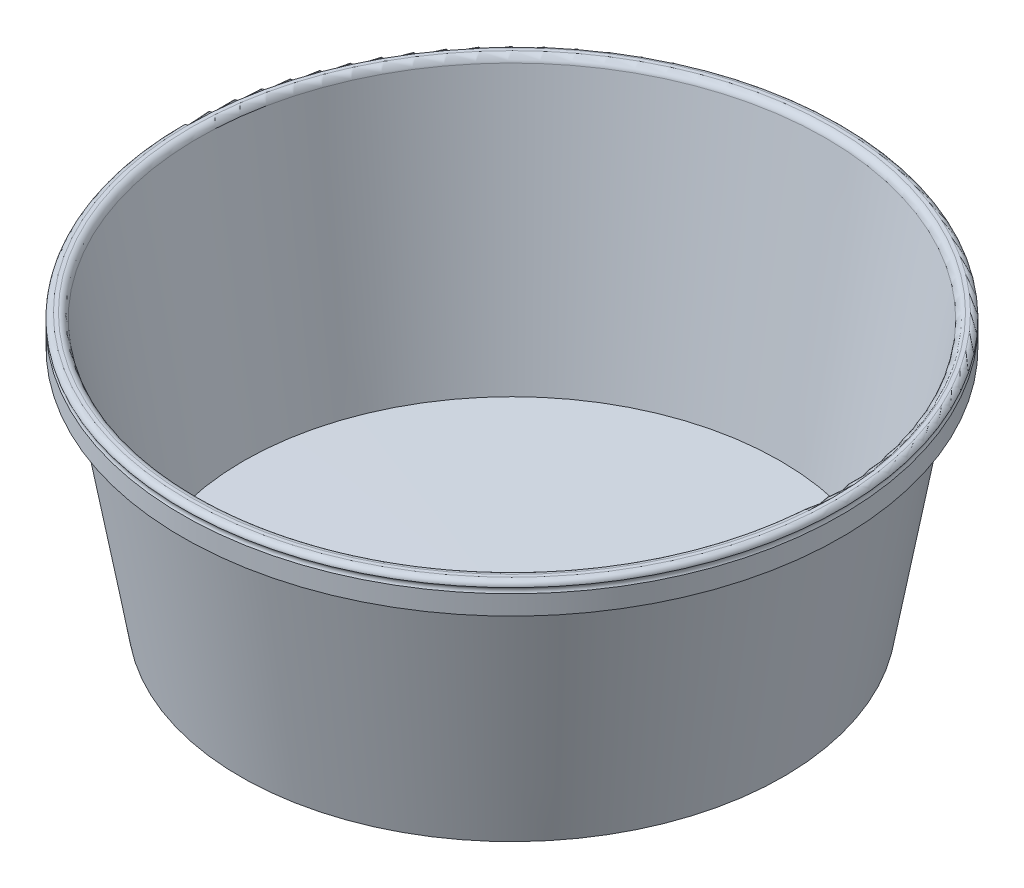
SolidWorks part; units mm, degrees
ref_plane "Alzado" through (0, 0, 0) normal (0, 0, 1) x (1, 0, 0)
ref_plane "Planta" through (0, 0, 0) normal (0, 1, 0) x (1, 0, 0)
ref_plane "Vista lateral" through (0, 0, 0) normal (1, 0, 0) x (0, 0, -1)
sketch "Croquis1" plane through (0, 0, 0) normal (0, 0, 1) x (1, 0, 0)
  line L0 (77, -1.344) -> (90, 72.3826)
  line L1 (90.9848, 73.209) -> (91.9848, 73.209)
  line L2 (92.4848, 72.709) -> (92.4848, 65.709)
  line L3 (0, 0) -> (0, 85.8592) construction
  line L4 (77, -1.344) -> (0, 0)
  line L5 (93.4859, 71.209) -> (93.4859, 65.709)
  line L6 (90.9859, 74.209) -> (91.9859, 74.209)
  line L7 (76.1646, -0.3293) -> (89.0163, 72.5563)
  line L8 (76.1646, -0.3293) -> (2, 0.9652)
  line L9 (0, 0) -> (91.0719, 0) construction
  line L10 (92.4848, 65.709) -> (93.4859, 65.709)
  line L11 (0, 2) -> (0, 0)
  arc A0 (90, 72.3826) -> (90.9848, 73.209) centre (90.9848, 72.209) cw
  arc A1 (91.9848, 73.209) -> (92.4848, 72.709) centre (91.9848, 72.709) cw
  arc A2 (91.9859, 74.209) -> (93.4859, 72.709) centre (91.9859, 72.709) cw
  arc A3 (89.0163, 72.5563) -> (90.9859, 74.209) centre (90.9859, 72.209) cw
  arc A4 (2, 0.9652) -> (0, 2) centre (0, -0.4502) ccw
  arc A5 (93.4859, 72.709) -> (93.4859, 71.209) centre (94.4818, 71.959) ccw
  dimension "D1" = 1
  dimension "D3" = 1
  dimension "D2" = 0.5
  dimension "D9" = 2
  dimension "D4" = 1.5
  dimension "D14" = 2
  dimension "D15" = 99
  dimension "D16" = 7
  dimension "D17" = 1.2467
  dimension "D5" = 154
  dimension "D6" = 1
  dimension "D7" = 99
  dimension "D8" = 1
  dimension "D10" = 2
  dimension "D11" = 180
  dimension "D12" = 7
  dimension "D13" = 1.0011
  dimension "D18" = 75.553
  dimension "D19" = 178.0326
revolve "Revolución1" add sketch "Croquis1" angle 360 about L3
sketch "Croquis2" plane through (0, 0, 0) normal (0, 0, 1) x (1, 0, 0)
  line L1 (88.1316, 61.8438) -> (90.069, 72.8315)
  line L2 (-91.9848, 73.209) -> (91.9848, 73.209) construction
  line L3 (90.2406, 73.209) -> (91.9848, 73.209)
  line L4 (92.4848, 65.709) -> (92.4848, 72.709) construction
  line L5 (92.4848, 66.8446) -> (92.4848, 72.709)
  line L6 (77, -1.344) -> (90, 72.3826) construction
  arc A1 (90.2406, 73.209) -> (90.069, 72.8315) centre (91.1124, 72.5849) ccw
  arc A2 (92.4848, 72.709) -> (91.9848, 73.209) centre (91.9848, 72.709) ccw construction
  arc A3 (92.4848, 72.709) -> (91.9848, 73.209) centre (91.9848, 72.709) ccw
  arc A4 (92.4848, 66.8446) -> (88.1316, 61.8438) centre (95.7161, 59.6365) ccw
  dimension "D1" = 0.01
extrude "Saliente-Extruir1" add sketch "Croquis2" along normal blind 0.5 and the other way blind 0.5
pattern_circular "MatrizC1" count 3 over 360 about axis through (0, -0.3293, 0) along (0, -1, 0) of "Saliente-Extruir1"
